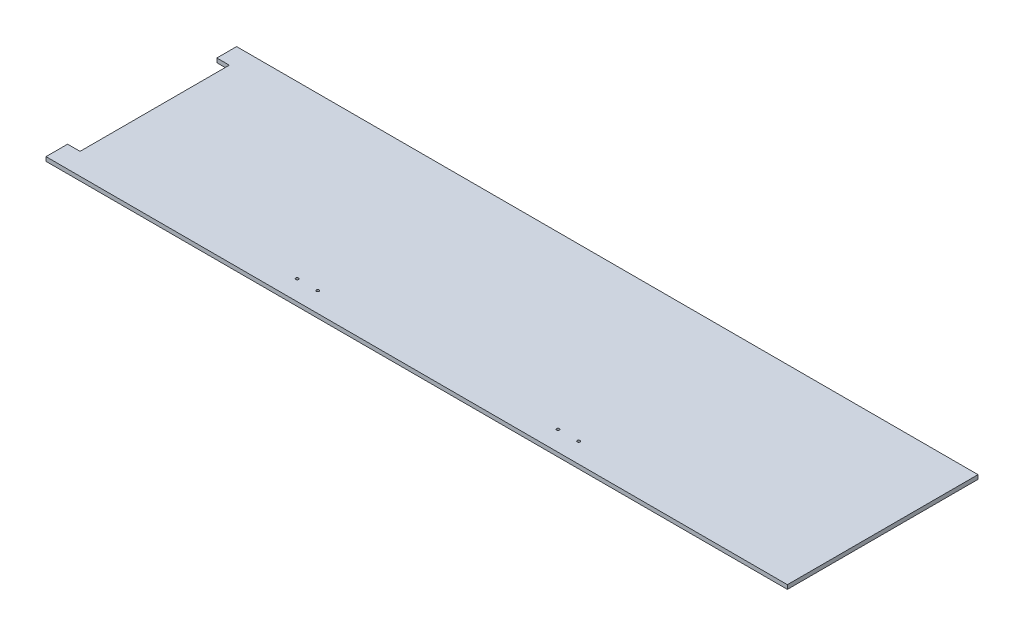
SolidWorks part; units mm, degrees
ref_plane "Front Plane" through (0, 0, 0) normal (0, 0, 1) x (1, 0, 0)
ref_plane "Top Plane" through (0, 0, 0) normal (0, 1, 0) x (1, 0, 0)
ref_plane "Right Plane" through (0, 0, 0) normal (1, 0, 0) x (0, 0, -1)
sketch "Sketch1" plane through (0, 0, 0) normal (0, 1, 0) x (1, 0, 0)
  line L0 (-260.9242, 55.0391) -> (-270, 55.0391)
  line L1 (-270, 69.412) -> (270, 69.412)
  line L2 (-270, 69.412) -> (-270, 55.0391)
  line L3 (-270, -69.412) -> (270, -69.412)
  line L4 (270, 69.412) -> (270, -69.412)
  line L5 (-270, 69.412) -> (270, -69.412) construction
  line L6 (-270, -69.412) -> (270, 69.412) construction
  line L7 (-260.9242, 55.0391) -> (-260.9242, -53.6808)
  line L8 (-260.9242, -53.6808) -> (-270, -53.6808)
  line L9 (-270, -53.6808) -> (-270, -69.412)
  line L10 (-270, 24.6382) -> (-270, 55.0391) construction
  line L11 (-270, -13.4618) -> (-270, -53.6808) construction
  circle A0 centre (103.4672, -54.974) radius 1
  circle A1 centre (88.4672, -54.974) radius 1
  circle A3 centre (-101.5479, -54.974) radius 1
  circle A4 centre (-86.5479, -54.974) radius 1
  point P4 (0, 0)
extrude "Boss-Extrude1" add sketch "Sketch1" along normal blind 3 contours L8 L9 L3 L4 L1 L2 L0 L7 A4 A3 A1 A0 region at (3.5412, 0, -0.0003)
